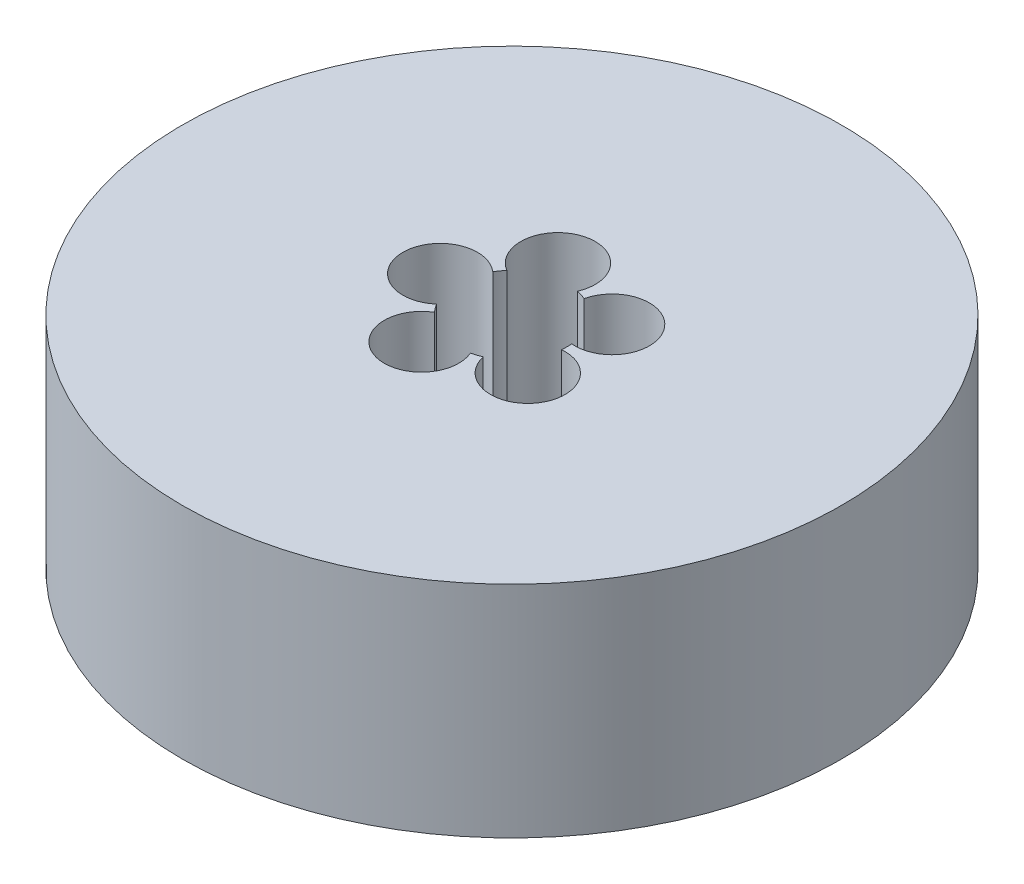
SolidWorks part; units mm, degrees
ref_plane "Front Plane" through (0, 0, 0) normal (0, 0, 1) x (1, 0, 0)
ref_plane "Top Plane" through (0, 0, 0) normal (0, 1, 0) x (1, 0, 0)
ref_plane "Right Plane" through (0, 0, 0) normal (1, 0, 0) x (0, 0, -1)
sketch "Sketch1" plane through (0, 0, 0) normal (0, 1, 0) x (1, 0, 0)
  circle A0 centre (0, 0) radius 45
  dimension "FLANGE_OD" = 90
extrude "Boss-Extrude1" add sketch "Sketch1" along normal blind 30
sketch "Sketch2" plane through (0, 0, 0) normal (0, 1, 0) x (1, 0, 0)
  circle A0 centre (0, 0) radius 7.5
  dimension "BORE_D" = 15
extrude "Cut-Extrude1" cut sketch "Sketch2" along normal through all
sketch "Sketch3" plane through (0, 30, 0) normal (0, 1, 0) x (1, 0, 0)
  circle A0 centre (0, 0) radius 9.7971 construction
  circle A1 centre (-9.7971, 0) radius 5.0868
  dimension "BOLT_D" = 10.1736
  dimension "BOLT_PCD" = 19.5941
extrude "Cut-Extrude2" cut sketch "Sketch3" against normal blind 26.6819
pattern_circular "CirPattern1" count 5 over 360 about axis through (0, 0, 0) along (0, 1, 0) of "Cut-Extrude2"
